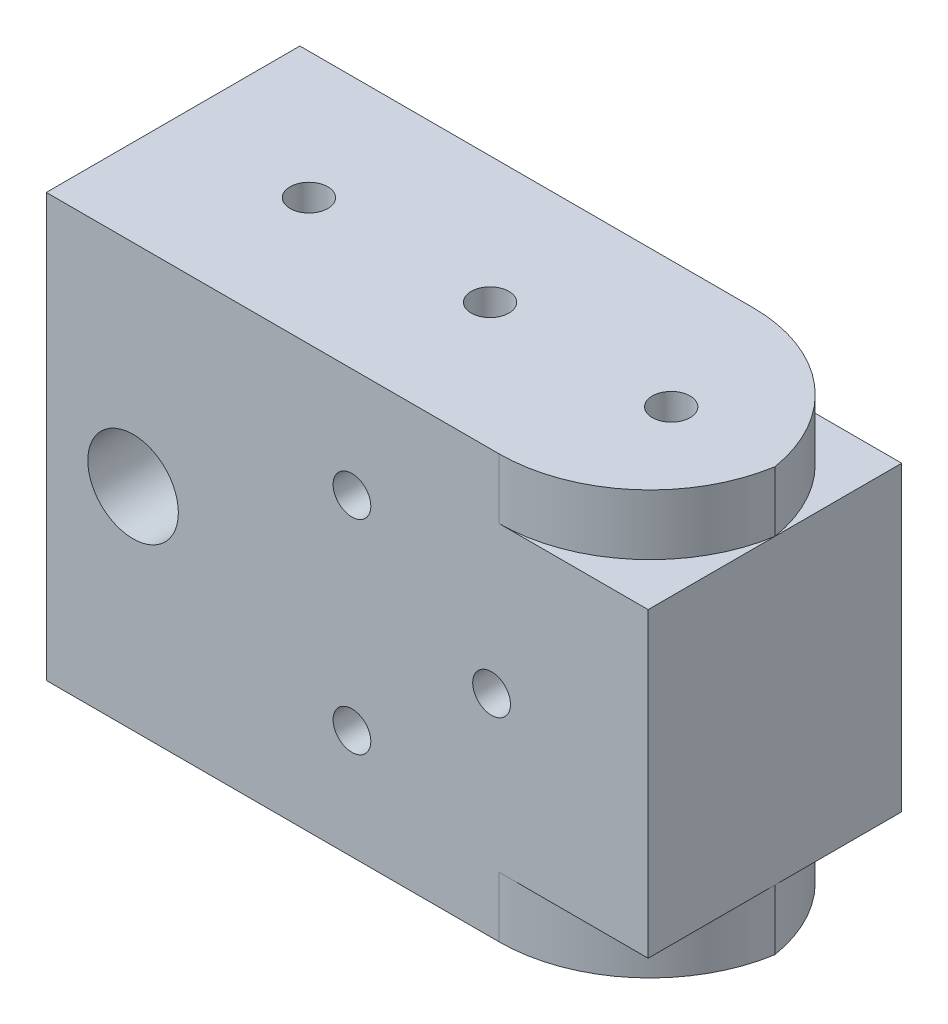
SolidWorks part; units mm, degrees
ref_plane "Front Plane" through (0, 0, 0) normal (0, 0, 1) x (1, 0, 0)
ref_plane "Top Plane" through (0, 0, 0) normal (0, 1, 0) x (1, 0, 0)
ref_plane "Right Plane" through (0, 0, 0) normal (1, 0, 0) x (0, 0, -1)
sketch "Sketch1" plane through (0, 0, 0) normal (0, 1, 0) x (1, 0, 0)
  line L1 (-20, -8.4) -> (20, -8.4)
  line L2 (-20, -8.4) -> (-20, 8.4)
  line L3 (-20, 8.4) -> (20, 8.4)
  line L4 (20, -8.4) -> (20, 8.4)
  line L5 (-20, -8.4) -> (20, 8.4) construction
  line L6 (-20, 8.4) -> (20, -8.4) construction
  point P0 (0, 0)
  dimension "D1" = 40
  dimension "D2" = 16.8
extrude "Boss-Extrude1" add sketch "Sketch1" along normal blind 28 contours L2 L1 L4 L3 region at (0, 0, 0)
fillet "Fillet2" radius 10 2 edges at (20, 14, -8.4) (20, 14, 8.4)
sketch "Sketch3" plane through (0, 0, 8.4) normal (0, 0, 1) x (1, 0, 0)
  line L0 (-20, 14) -> (19.8712, 14)
  line L1 (-20, 28) -> (-20, 0) construction
  line L2 (19.8712, 28) -> (19.8712, 0) construction
  line L4 (-20, 4) -> (19.8712, 4)
  line L5 (-20, 4) -> (-20, 24)
  line L6 (-20, 24) -> (19.8712, 24)
  line L7 (19.8712, 4) -> (19.8712, 24)
  line L8 (-20, 4) -> (19.8712, 24) construction
  line L9 (-20, 24) -> (19.8712, 4) construction
  point P6 (-0.0644, 14)
  line M4 (10, 0) -> (10, 28)
  line M6 (-20, 28) -> (-20, 0)
  dimension "D1" = 39.8712
  dimension "D2" = 20
extrude "Boss-Extrude2" add sketch "Sketch3" against normal blind 16.8 contours L4 L7 L0 M4 | L0 L7 L6 M4 | L6 L0 M6 M4 | L4 L0 M6 M4 region at (-5, 19, 8.4) region at (-5, 9, 8.4) region at (14.9356, 19, 8.4) region at (14.9356, 9, 8.4)
sketch "Sketch2" plane through (0, 0, 8.4) normal (0, 0, 1) x (1, 0, 0)
  line L0 (-20, 14) -> (-14.25, 14)
  line L1 (-20, 28) -> (-20, 0) construction
  line L2 (-14.25, 14) -> (9.5, 14)
  line L3 (9.5, 14) -> (9.5, 20.75)
  line L4 (9.5, 20.75) -> (0.25, 20.75)
  circle A0 centre (-14.25, 14) radius 3
  circle A1 centre (9.5, 14) radius 1.25
  circle A2 centre (0.25, 20.75) radius 1.25
  circle A3 centre (0.25, 7.25) radius 1.25
  dimension "D1" = 6.75
  dimension "D3" = 2.5
  dimension "D4" = 6
  dimension "D2" = 9.25
extrude "Cut-Extrude1" cut sketch "Sketch2" against normal blind 16.8 contours L0 A0 L2 | L2 A0 L0 | A2 | L2 A1 L3 | L3 A1 L2 | A3 | A0 region at (-14.25, 15.2732, 8.4) region at (-0.9646, 20.75, 8.4) region at (8.9695, 14.5305, 8.4) region at (9.6768, 13.8232, 8.4) region at (-14.25, 12.7268, 8.4) region at (0.25, 7.25, 8.4)
sketch "Sketch4" plane through (0, 28, 0) normal (0, 1, 0) x (1, 0, 0)
  line L0 (-20, 0) -> (-11, 0)
  line L1 (-20, -8.4) -> (-20, 8.4) construction
  line L2 (-11, 0) -> (1, 0)
  line L3 (1, 0) -> (13, 0)
  circle A0 centre (-11, 0) radius 1.25
  circle A1 centre (1, 0) radius 1.25
  circle A2 centre (13, 0) radius 1.25
extrude "Cut-Extrude2" cut sketch "Sketch4" against normal through all contours L0 A0 L2 | L2 A0 L0 | L2 A1 L3 | L3 A1 L2 | A2 region at (-11, 28, -0.5305) region at (13, 28, -1.2146) region at (1, 28, -0.5305) region at (1, 28, 0.5305) region at (-11, 28, 0.5305)
